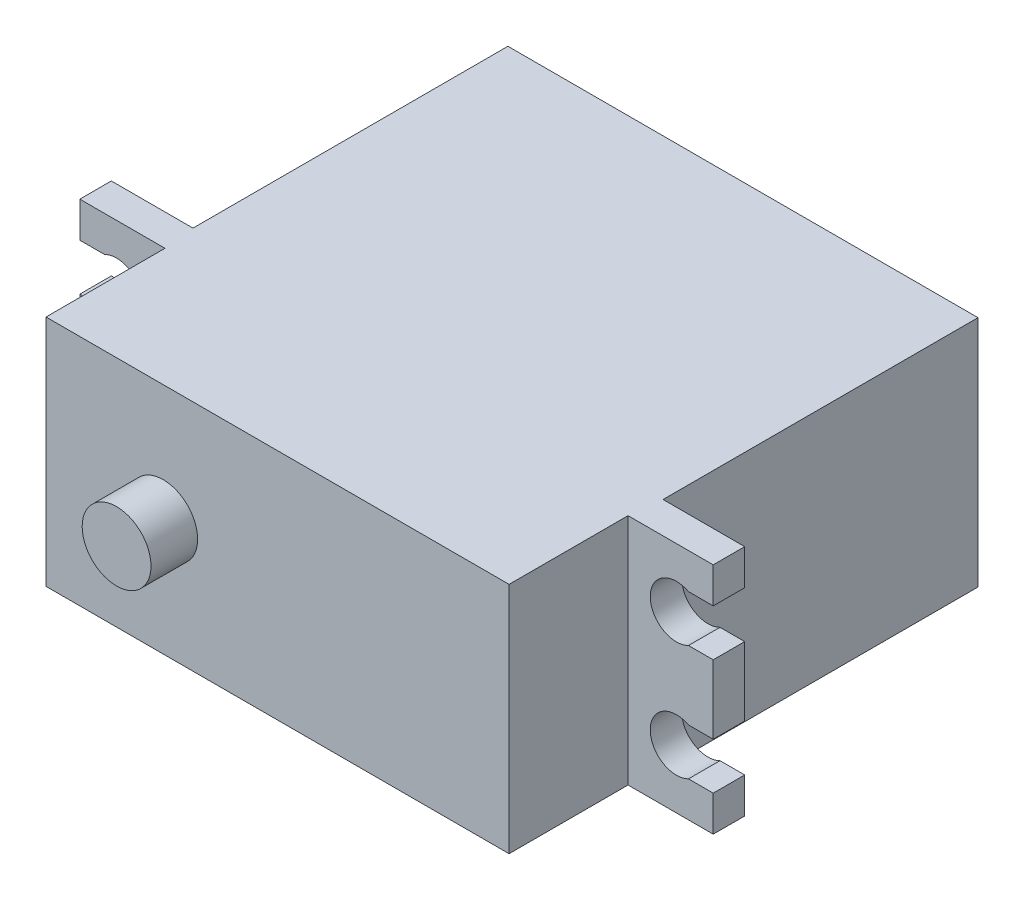
SolidWorks part; units mm, degrees
ref_plane "Front Plane" through (0, 0, 0) normal (0, 0, 1) x (1, 0, 0)
ref_plane "Top Plane" through (0, 0, 0) normal (0, 1, 0) x (1, 0, 0)
ref_plane "Right Plane" through (0, 0, 0) normal (1, 0, 0) x (0, 0, -1)
other "Bounding Box"
ref_plane "Default Plane" through (-8.9266, -12.7485, 0) normal (-0.1736, 0.9848, 0) x (0.9848, 0.1736, 0)
sketch "Sketch1" plane through (0, 0, 0) normal (0, 1, 0) x (1, 0, 0)
  line L1 (20.15, -13.5) -> (-20.15, -13.5)
  line L2 (20.15, -13.5) -> (20.15, 13.5)
  line L3 (20.15, 13.5) -> (-20.15, 13.5)
  line L4 (-20.15, -13.5) -> (-20.15, 13.5)
  line L5 (20.15, -13.5) -> (-20.15, 13.5) construction
  line L6 (20.15, 13.5) -> (-20.15, -13.5) construction
  point P0 (0, 0)
  dimension "D1" = 40.3
  dimension "D2" = 27
extrude "Boss-Extrude1" add sketch "Sketch1" along normal blind 20
sketch "Sketch2" plane through (0, 0, 13.5) normal (0, 0, 1) x (1, 0, 0)
  line L0 (-20.15, 10) -> (20.15, 10) construction
  line L1 (-20.15, 20) -> (-20.15, 0) construction
  line L2 (20.15, 20) -> (20.15, 0) construction
  line L3 (0, 0) -> (0, 20) construction
  line L4 (-20.15, 20) -> (20.15, 20) construction
  line L5 (-20.15, 20) -> (20.15, 20)
  line L6 (27.15, 0) -> (-27.15, 0)
  line L7 (27.15, 0) -> (27.15, 20)
  line L8 (27.15, 20) -> (-27.15, 20)
  line L9 (-27.15, 0) -> (-27.15, 20)
  line L10 (27.15, 0) -> (-27.15, 20) construction
  line L11 (27.15, 20) -> (-27.15, 0) construction
  line L13 (24, 5.05) -> (-24, 5.05)
  line L14 (24, 5.05) -> (24, 14.95)
  line L15 (24, 14.95) -> (-24, 14.95)
  line L16 (-24, 5.05) -> (-24, 14.95)
  line L17 (24, 5.05) -> (-24, 14.95) construction
  line L18 (24, 14.95) -> (-24, 5.05) construction
  line L19 (-24, 12.95) -> (-30.3, 12.95)
  line L20 (-24, 12.95) -> (-24, 16.95)
  line L21 (-24, 16.95) -> (-30.3, 16.95)
  line L22 (-30.3, 12.95) -> (-30.3, 16.95)
  line L23 (-24, 12.95) -> (-30.3, 16.95) construction
  line L24 (-24, 16.95) -> (-30.3, 12.95) construction
  line L29 (-24, 3.05) -> (-30.3, 3.05)
  line L30 (-24, 3.05) -> (-24, 7.05)
  line L31 (-24, 7.05) -> (-30.3, 7.05)
  line L32 (-30.3, 3.05) -> (-30.3, 7.05)
  line L33 (-24, 3.05) -> (-30.3, 7.05) construction
  line L34 (-24, 7.05) -> (-30.3, 3.05) construction
  line L35 (24, 16.95) -> (30.3, 16.95)
  line L36 (24, 16.95) -> (24, 12.95)
  line L37 (24, 12.95) -> (30.3, 12.95)
  line L38 (30.3, 16.95) -> (30.3, 12.95)
  line L39 (24, 16.95) -> (30.3, 12.95) construction
  line L40 (24, 12.95) -> (30.3, 16.95) construction
  line L41 (24, 7.05) -> (30.3, 7.05)
  line L42 (24, 7.05) -> (24, 3.05)
  line L43 (24, 3.05) -> (30.3, 3.05)
  line L44 (30.3, 7.05) -> (30.3, 3.05)
  line L45 (24, 7.05) -> (30.3, 3.05) construction
  line L46 (24, 3.05) -> (30.3, 7.05) construction
  circle A0 centre (-24, 14.95) radius 2.25
  circle A1 centre (-24, 5.05) radius 2.25
  circle A2 centre (24, 5.05) radius 2.25
  circle A3 centre (24, 14.95) radius 2.25
  point P11 (0, 10)
  point P16 (0, 10)
  point P25 (-27.15, 14.95)
  point P30 (-27.15, 5.05)
  point P35 (27.15, 14.95)
  point P40 (27.15, 5.05)
  point P45 (0, 0)
  line M3 (-20.15, 0) -> (20.15, 0)
  line M4 (20.15, 0) -> (20.15, 20)
  line M5 (20.15, 20) -> (-20.15, 20)
  line M6 (-20.15, 20) -> (-20.15, 0)
  dimension "D4" = 4.5
  dimension "D1" = 54.3
  dimension "D2" = 48
  dimension "D3" = 9.9
  dimension "D5" = 4
extrude "Boss-Extrude2" add sketch "Sketch2" along normal blind 2.7 contours L13 M4 M6 M3 | A1 L29 L9 L6 L13 M6 | L15 L13 M4 M6 | A1 L13 L15 A0 L16 M6 | A1 L16 A0 L19 L9 L31 | L15 M4 M5 M6 | A0 L15 L8 L9 L21 M6 | A3 L35 L7 L8 L15 M4 | A3 L14 A2 L41 L7 L37 | A2 L13 L6 L7 L43 M4 | A3 L15 L13 A2 L14 M4 region at (-23.2544, 18.1145, 13.5) region at (0, 17.475, 13.5) region at (23.2544, 18.1145, 13.5) region at (-21.8192, 10, 13.5) region at (0, 10, 13.5) region at (21.8192, 10, 13.5) region at (-23.2544, 1.8855, 13.5) region at (0, 2.525, 13.5) region at (23.2544, 1.8855, 13.5) region at (-25.5976, 10, 13.5) region at (25.5976, 10, 13.5)
sketch "Sketch3" plane through (0, 0, 16.2) normal (0, 0, 1) x (1, 0, 0)
  line L0 (-27.15, 10) -> (27.15, 10) construction
  line L1 (-27.15, 7.05) -> (-27.15, 12.95) construction
  line L2 (27.15, 7.05) -> (27.15, 12.95) construction
  line L3 (0, 20) -> (0, 0) construction
  line L4 (27.15, 20) -> (-27.15, 20) construction
  line L5 (27.15, 20) -> (-27.15, 20)
  line L6 (19.85, 0) -> (-19.85, 0)
  line L7 (19.85, 0) -> (19.85, 20)
  line L8 (19.85, 20) -> (-19.85, 20)
  line L9 (-19.85, 0) -> (-19.85, 20)
  line L10 (19.85, 0) -> (-19.85, 20) construction
  line L11 (19.85, 20) -> (-19.85, 0) construction
  point P11 (0, 10)
  dimension "D2" = 39.7
extrude "Boss-Extrude3" add sketch "Sketch3" along normal blind 10.2 contours L7 L6 L9 L8
sketch "Sketch4" plane through (0, 0, 26.4) normal (0, 0, 1) x (1, 0, 0)
  line L0 (-27.15, 10) -> (27.15, 10) construction
  line L1 (-27.15, 7.05) -> (-27.15, 12.95) construction
  line L2 (27.15, 7.05) -> (27.15, 12.95) construction
  arc A0 (-25.0308, 12.95) -> (-25.0308, 16.95) centre (-24, 14.95) ccw construction
  arc A1 (-25.0308, 12.95) -> (-25.0308, 16.95) centre (-24, 14.95) ccw
  circle A2 centre (-9.8, 10) radius 2.95
  point P11 (0, 0)
  dimension "D2" = 5.9
  dimension "D1" = 14.2
extrude "Boss-Extrude4" add sketch "Sketch4" along normal blind 4 contours A2 L0 | L0 A2 region at (-9.8, 11.252, 26.4) region at (-9.8, 8.748, 26.4)
sketch "Sketch5" plane through (-20.15, 0, 0) normal (-1, 0, 0) x (0, 0, 1)
  line L0 (-13.5, 10) -> (6.1644, 10) construction
  line L1 (-6.9171, 4.3103) -> (-10.4185, 4.3103)
  line L2 (-6.9171, 4.3103) -> (-6.9171, 15.6897)
  line L3 (-6.9171, 15.6897) -> (-10.4185, 15.6897)
  line L4 (-10.4185, 4.3103) -> (-10.4185, 15.6897)
  line L5 (-6.9171, 4.3103) -> (-10.4185, 15.6897) construction
  line L6 (-6.9171, 15.6897) -> (-10.4185, 4.3103) construction
  line L7 (-13.5, 20) -> (-13.5, 0) construction
  point P0 (-8.6678, 10)
  dimension "D1" = 11.3794
  dimension "D2" = 3.5014
  dimension "D3" = 4.8322
extrude "Boss-Extrude5" add sketch "Sketch5" along normal blind 4
